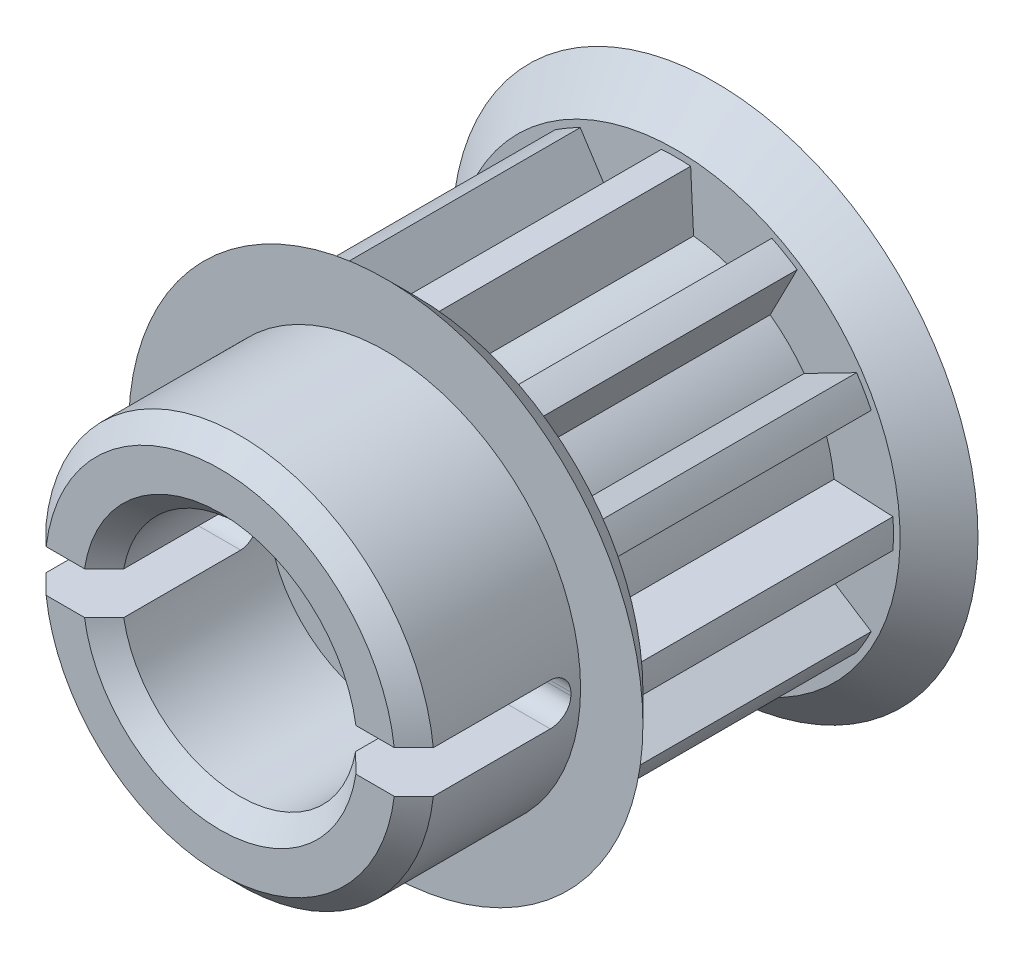
SolidWorks part; units mm, degrees
material "ABS"
ref_plane "Alzado" through (0, 0, 0) normal (0, 0, 1) x (1, 0, 0)
ref_plane "Planta" through (0, 0, 0) normal (0, 1, 0) x (1, 0, 0)
ref_plane "Vista lateral" through (0, 0, 0) normal (1, 0, 0) x (0, 0, -1)
sketch "Croquis1" plane through (0, 0, 0) normal (0, 0, 1) x (1, 0, 0)
  line L0 (0, 0) -> (0, 4.6049) construction
  line L1 (0.375, 5.5679) -> (0.45, 4.0556)
  line L2 (-0.375, 5.5679) -> (-0.45, 4.0556)
  line L3 (2.4592, 5.0094) -> (1.6381, 3.7373)
  line L4 (3.1087, 4.6344) -> (2.4175, 3.2873)
  line L5 (4.6344, 3.1087) -> (3.2873, 2.4175)
  line L6 (5.0094, 2.4592) -> (3.7373, 1.6381)
  line L7 (5.5679, 0.375) -> (4.0556, 0.45)
  line L8 (5.5679, -0.375) -> (4.0556, -0.45)
  line L9 (5.0094, -2.4592) -> (3.7373, -1.6381)
  line L10 (4.6344, -3.1087) -> (3.2873, -2.4175)
  line L11 (3.1087, -4.6344) -> (2.4175, -3.2873)
  line L12 (2.4592, -5.0094) -> (1.6381, -3.7373)
  line L13 (0.375, -5.5679) -> (0.45, -4.0556)
  line L14 (-0.375, -5.5679) -> (-0.45, -4.0556)
  line L15 (-2.4592, -5.0094) -> (-1.6381, -3.7373)
  line L16 (-3.1087, -4.6344) -> (-2.4175, -3.2873)
  line L17 (-4.6344, -3.1087) -> (-3.2873, -2.4175)
  line L18 (-5.0094, -2.4592) -> (-3.7373, -1.6381)
  line L19 (-5.5679, -0.375) -> (-4.0556, -0.45)
  line L20 (-5.5679, 0.375) -> (-4.0556, 0.45)
  line L21 (-5.0094, 2.4592) -> (-3.7373, 1.6381)
  line L22 (-4.6344, 3.1087) -> (-3.2873, 2.4175)
  line L23 (-3.1087, 4.6344) -> (-2.4175, 3.2873)
  line L24 (-2.4592, 5.0094) -> (-1.6381, 3.7373)
  circle A0 centre (0, 0) radius 1.85
  arc A1 (1.6381, 3.7373) -> (0.45, 4.0556) centre (0, 0) ccw
  arc A2 (3.1087, 4.6344) -> (2.4592, 5.0094) centre (0, 0) ccw
  arc A3 (5.0094, 2.4592) -> (4.6344, 3.1087) centre (0, 0) ccw
  arc A4 (5.5679, -0.375) -> (5.5679, 0.375) centre (0, 0) ccw
  arc A5 (4.6344, -3.1087) -> (5.0094, -2.4592) centre (0, 0) ccw
  arc A6 (2.4592, -5.0094) -> (3.1087, -4.6344) centre (0, 0) ccw
  arc A7 (-0.375, -5.5679) -> (0.375, -5.5679) centre (0, 0) ccw
  arc A8 (-3.1087, -4.6344) -> (-2.4592, -5.0094) centre (0, 0) ccw
  arc A9 (-5.0094, -2.4592) -> (-4.6344, -3.1087) centre (0, 0) ccw
  arc A10 (-5.5679, 0.375) -> (-5.5679, -0.375) centre (0, 0) ccw
  arc A11 (-4.6344, 3.1087) -> (-5.0094, 2.4592) centre (0, 0) ccw
  arc A12 (-2.4592, 5.0094) -> (-3.1087, 4.6344) centre (0, 0) ccw
  arc A13 (0.375, 5.5679) -> (-0.375, 5.5679) centre (0, 0) ccw
  arc A14 (3.2873, 2.4175) -> (2.4175, 3.2873) centre (0, 0) ccw
  arc A15 (4.0556, 0.45) -> (3.7373, 1.6381) centre (0, 0) ccw
  arc A16 (3.7373, -1.6381) -> (4.0556, -0.45) centre (0, 0) ccw
  arc A17 (2.4175, -3.2873) -> (3.2873, -2.4175) centre (0, 0) ccw
  arc A18 (0.45, -4.0556) -> (1.6381, -3.7373) centre (0, 0) ccw
  arc A19 (-1.6381, -3.7373) -> (-0.45, -4.0556) centre (0, 0) ccw
  arc A20 (-3.2873, -2.4175) -> (-2.4175, -3.2873) centre (0, 0) ccw
  arc A21 (-4.0556, -0.45) -> (-3.7373, -1.6381) centre (0, 0) ccw
  arc A22 (-3.7373, 1.6381) -> (-4.0556, 0.45) centre (0, 0) ccw
  arc A23 (-2.4175, 3.2873) -> (-3.2873, 2.4175) centre (0, 0) ccw
  arc A24 (-0.45, 4.0556) -> (-1.6381, 3.7373) centre (0, 0) ccw
  dimension "D1" = 0.9
  dimension "D2" = 3.7
  dimension "D4" = 1.5
  dimension "D3" = 0.75
  dimension "D6" = 1.23
  dimension "D5" = 12
extrude "Saliente-Extruir1" add sketch "Croquis1" along normal blind 6.7
sketch "Croquis2" plane through (0, 0, 6.7) normal (0, 0, 1) x (1, 0, 0)
  circle A0 centre (0, 0) radius 3.025
  circle A1 centre (0, 0) radius 5
  dimension "D1" = 10
  dimension "D2" = 6.05
extrude "Saliente-Extruir2" add sketch "Croquis2" along normal blind 5
chamfer "Chaflán1" distance 0.5 angle 45 1 edges at (5, 0, 11.7)
sketch "Croquis3" plane through (0, 0, 0) normal (0, 0, -1) x (-1, 0, 0)
  circle A0 centre (0, 0) radius 1.85
  circle A1 centre (0, 0) radius 6.75
  circle A2 centre (0, 0) radius 1.85 construction
  dimension "D1" = 13.5
extrude "Saliente-Extruir3" add sketch "Croquis3" along normal blind 1
chamfer "Chaflán2" distance 0.5 angle 45 1 edges at (3.025, 0, 11.7)
sketch "Croquis4" plane through (0, 0, 6.7) normal (0, 0, 1) x (1, 0, 0)
  circle A0 centre (0, 0) radius 1.85
  circle A1 centre (0, 0) radius 4.8926
  circle A2 centre (0, 0) radius 1.85 construction
extrude "Saliente-Extruir4" add sketch "Croquis4" along normal blind 0.1
chamfer "Chaflán3" distance 0.5 angle 45 12 edges at (3.9415, 1.0561, 6.7) (2.8853, 2.8853, 6.7) (1.0561, 3.9415, 6.7) (-1.0561, 3.9415, 6.7) (-2.8853, 2.8853, 6.7) (-3.9415, -1.0561, 6.7) (-3.9415, 1.0561, 6.7) (-2.8853, -2.8853, 6.7) (-1.0561, -3.9415, 6.7) (1.0561, -3.9415, 6.7) (2.8853, -2.8853, 6.7) (3.9415, -1.0561, 6.7)
chamfer "Chaflán4" distance 1 angle 45 1 edges at (-6.75, 0, 0)
sketch "Croquis6" plane through (0, 0, 6.7) normal (0, 0, 1) x (1, 0, 0)
  circle A0 centre (0, 0) radius 6.75
  circle A2 centre (0, 0) radius 1.85
  circle A4 centre (0, 0) radius 1.85 construction
  dimension "D1" = 13.5
extrude "Saliente-Extruir5" add sketch "Croquis6" along normal blind 0.75
chamfer "Chaflán5" distance 0.9 angle 45 1 edges at (6.75, 0, 6.7)
sketch "Croquis8" plane through (0, 0, -1) normal (0, 0, -1) x (-1, 0, 0)
  line L1 (-1.4818, -2.3418) -> (1.2872, -2.4542)
  line L2 (1.2872, -2.4542) -> (2.769, -0.1124)
  line L3 (2.769, -0.1124) -> (1.4818, 2.3418)
  line L4 (1.4818, 2.3418) -> (-1.2872, 2.4542)
  line L5 (-1.2872, 2.4542) -> (-2.769, 0.1124)
  line L6 (-2.769, 0.1124) -> (-1.4818, -2.3418)
  circle A0 centre (0, 0) radius 2.4 construction
  dimension "D1" = 4.8
extrude "Cortar-Extruir1" cut sketch "Croquis8" against normal blind 5.5
chamfer "Chaflán6" distance 1 angle 45 6 edges at (-0.0973, 2.398, -1) (2.0281, 1.2833, -1) (2.1254, -1.1147, -1) (0.0973, -2.398, -1) (-2.0281, -1.2833, -1) (-2.1254, 1.1147, -1)
chamfer "Chaflán7" distance 1 angle 45 1 edges at (-1.85, 0, 4.5)
sketch "Croquis9" plane through (0, 0, 11.7) normal (0, 0, 1) x (1, 0, 0)
  line L0 (5.7484, 0) -> (-6.3843, 0) construction
  line L1 (5.7026, -0.5408) -> (5.7026, 0.5408)
  line L2 (5.7026, 0.5408) -> (-5.9897, 0.5408)
  line L3 (-5.9897, 0.5408) -> (-5.9897, -0.5408)
  line L4 (-5.9897, -0.5408) -> (5.7026, -0.5408)
extrude "Cortar-Extruir2" cut sketch "Croquis9" along direction (0, 0, 1) on the side against the normal blind 4
fillet "Redondeo1" radius 0.5 4 edges at (3.9735, -0.5408, 7.7) (3.9735, 0.5408, 7.7) (-3.9735, -0.5408, 7.7) (-3.9735, 0.5408, 7.7)
